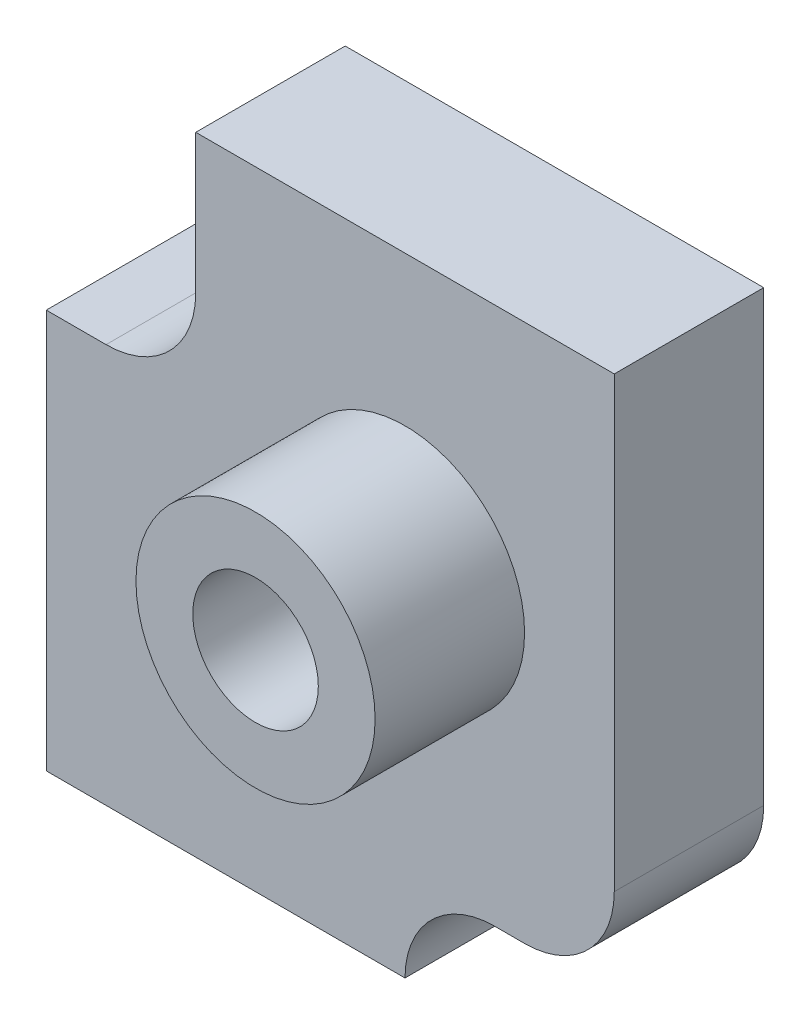
SolidWorks part; units mm, degrees
ref_plane "Front Plane" through (0, 0, 0) normal (0, 0, 1) x (1, 0, 0)
ref_plane "Top Plane" through (0, 0, 0) normal (0, 1, 0) x (1, 0, 0)
ref_plane "Right Plane" through (0, 0, 0) normal (1, 0, 0) x (0, 0, -1)
sketch "Sketch1" plane through (0, 0, 0) normal (0, 0, 1) x (1, 0, 0)
  line L1 (-7, 9) -> (7, 9)
  line L2 (-7, 9) -> (-7, -9)
  line L3 (-7, -9) -> (7, -9)
  line L4 (7, 9) -> (7, -9)
  point P4 (7, 0)
  point P6 (0, 9)
  dimension "D1" = 14
  dimension "D2" = 18
extrude "Extrude1" add sketch "Sketch1" along normal blind 5
sketch "Sketch2" plane through (0, 0, 5) normal (0, 0, 1) x (1, 0, 0)
  circle A0 centre (0, 0) radius 4
  dimension "D1" = 8
extrude "Extrude2" add sketch "Sketch2" along normal blind 5
sketch "Sketch3" plane through (0, 0, 10) normal (0, 0, 1) x (1, 0, 0)
  circle A0 centre (0, 0) radius 2.1
  dimension "D1" = 4.2
extrude "Extrude3" cut sketch "Sketch3" against normal offset from surface (6 mm away) 4 up to face at (0, 0, 0)
sketch "Sketch4" plane through (0, 0, 0) normal (0, 0, 1) x (1, 0, 0)
  line L0 (-7, 1.349) -> (-12, 1.349)
  line L2 (-12, 1.349) -> (-12, -12)
  line L3 (-12, -12) -> (0, -12)
  line L4 (0, -12) -> (0, -9)
  line L5 (-7, -9) -> (7, -9) construction
  line L6 (0, -9) -> (-7, -9)
  line L7 (-7, -9) -> (-7, 1.349)
  line L8 (-7, 9) -> (-7, -9) construction
  dimension "D1" = 5
  dimension "D2" = 3
extrude "Extrude5" add sketch "Sketch4" along normal up to surface (5 mm away) up to face at (0, 0, 5)
fillet "Fillet1" radius 3 3 edges at (0, -9, 2.5) (7, -9, 2.5) (-7, 1.349, 2.5)
